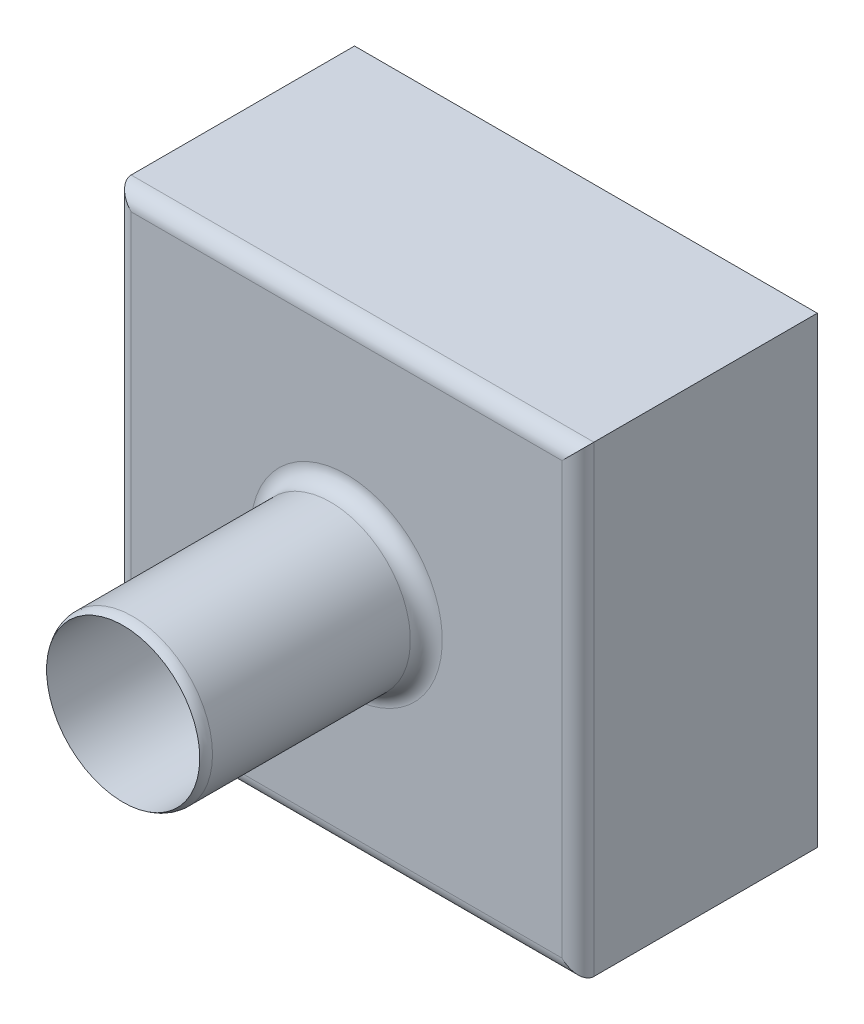
SolidWorks part; units mm, degrees
ref_plane "Front Plane" through (0, 0, 0) normal (0, 0, 1) x (1, 0, 0)
ref_plane "Top Plane" through (0, 0, 0) normal (0, 1, 0) x (1, 0, 0)
ref_plane "Right Plane" through (0, 0, 0) normal (1, 0, 0) x (0, 0, -1)
sketch "Sketch1" plane through (0, 0, 0) normal (0, 0, 1) x (1, 0, 0)
  line L1 (0, 0) -> (-29, 0)
  line L2 (0, 0) -> (0, -29)
  line L3 (0, -29) -> (-29, -29)
  line L4 (-29, 0) -> (-29, -29)
  dimension "D1" = 29
  dimension "D2" = 29
extrude "Boss-Extrude1" add sketch "Sketch1" along normal blind 15
sketch "Sketch2" plane through (0, 0, 15) normal (0, 0, 1) x (1, 0, 0)
  line L0 (0, -29) -> (0, 0) construction
  line L1 (0, 0) -> (-29, 0) construction
  circle A0 centre (-14.5, -14.5) radius 5
  dimension "D1" = 14.5
  dimension "D2" = 14.5
extrude "Cut-Extrude1" cut sketch "Sketch2" against normal through all
sketch "Sketch3" plane through (0, 0, 0) normal (0, 0, -1) x (-1, 0, 0)
  line L0 (0, -29) -> (0, 0) construction
  line L1 (1.5, -5.3) -> (23.7, -5.3)
  line L2 (1.5, -5.3) -> (1.5, -27.5)
  line L3 (1.5, -27.5) -> (23.7, -27.5)
  line L4 (23.7, -5.3) -> (23.7, -27.5)
  line L5 (29, -29) -> (0, -29) construction
  dimension "D1" = 22.2
  dimension "D2" = 22.2
  dimension "D3" = 1.5
  dimension "D4" = 1.5
extrude "Cut-Extrude2" cut sketch "Sketch3" against normal blind 13
fillet "Fillet2" radius 1 5 edges at (-19.5, -14.5, 13) (-12.6, -5.3, 13) (-23.7, -16.4, 13) (-12.6, -27.5, 13) (-1.5, -16.4, 13)
fillet "Fillet3" radius 1 12 edges at (-23.4071, -5.5929, 12.7071) (-23.4071, -27.2071, 12.7071) (-1.7929, -5.5929, 12.7071) (-1.7929, -27.2071, 12.7071) (-12.6, -5.3, 0) (-23.7, -16.4, 0) (-23.7, -5.3, 6) (-12.6, -27.5, 0) (-23.7, -27.5, 6) (-1.5, -16.4, 0) (-1.5, -5.3, 6) (-1.5, -27.5, 6)
ref_plane "Plane1" through (0, 0, 14) normal (0, 0, 1) x (1, 0, 0)
sketch "Sketch7" plane through (0, 0, 14) normal (0, 0, 1) x (1, 0, 0)
  circle A0 centre (-14.5, -14.5) radius 5
extrude "Boss-Extrude3" add sketch "Sketch7" along normal blind 15
sketch "Sketch8" plane through (0, 0, 29) normal (0, 0, 1) x (1, 0, 0)
  circle A0 centre (-14.5, -14.5) radius 4.8
extrude "Cut-Extrude4" cut sketch "Sketch8" against normal blind 15
fillet "Fillet4" radius 1 6 edges at (-9.5, -14.5, 29) (-14.5, -29, 15) (-29, -14.5, 15) (-14.5, 0, 15) (0, -14.5, 15) (-9.5, -14.5, 15)
